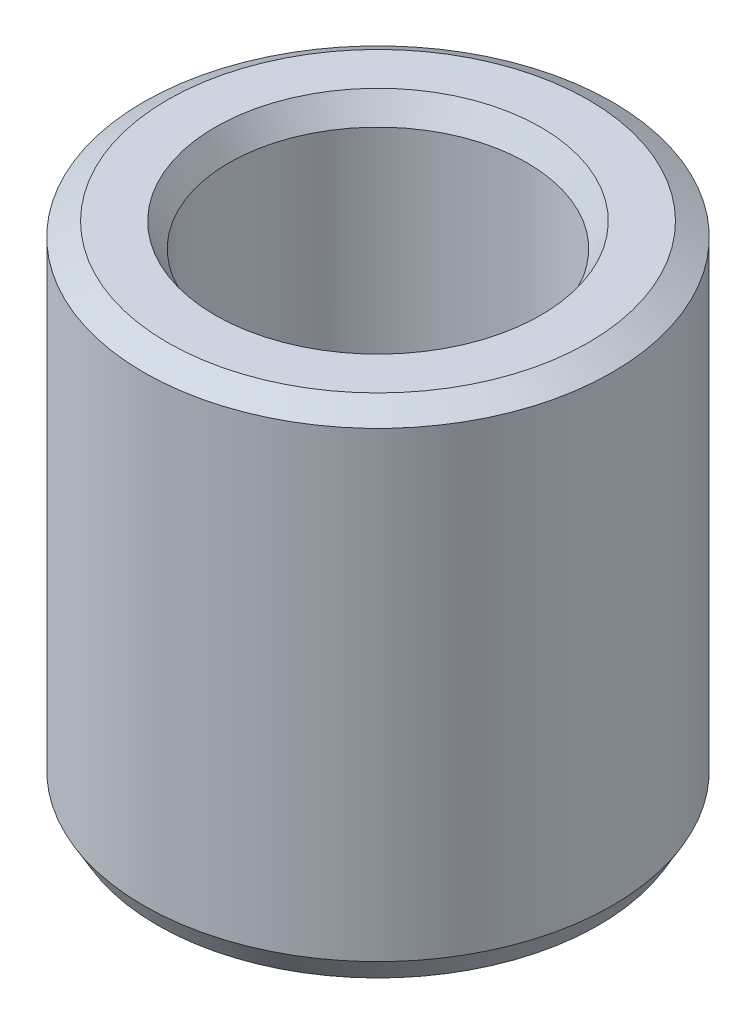
SolidWorks part; units mm, degrees
ref_plane "Front Plane" through (0, 0, 0) normal (0, 0, 1) x (1, 0, 0)
ref_plane "Top Plane" through (0, 0, 0) normal (0, 1, 0) x (1, 0, 0)
ref_plane "Right Plane" through (0, 0, 0) normal (1, 0, 0) x (0, 0, -1)
sketch "Sketch1" plane through (0, 0, 0) normal (0, 1, 0) x (1, 0, 0)
  circle A0 centre (0, 0) radius 45
  dimension "SLEEVE_OD" = 90
extrude "Boss-Extrude1" add sketch "Sketch1" along normal blind 95.9526
sketch "Sketch2" plane through (0, 0, 0) normal (0, 1, 0) x (1, 0, 0)
  circle A0 centre (0, 0) radius 28.6296
  dimension "BORE_D" = 57.2591
extrude "Cut-Extrude1" cut sketch "Sketch2" along normal through all
chamfer "Chamfer1" distance 2.6521 angle 60 4 edges at (0, 95.9526, 28.6296) (0, 0, 28.6296) (0, 0, 45) (0, 95.9526, 45) first distance on face at (0, 95.9526, 28.6296) first distance on face at (0, 0, 28.6296) first distance on face at (0, 95.9526, 45)
